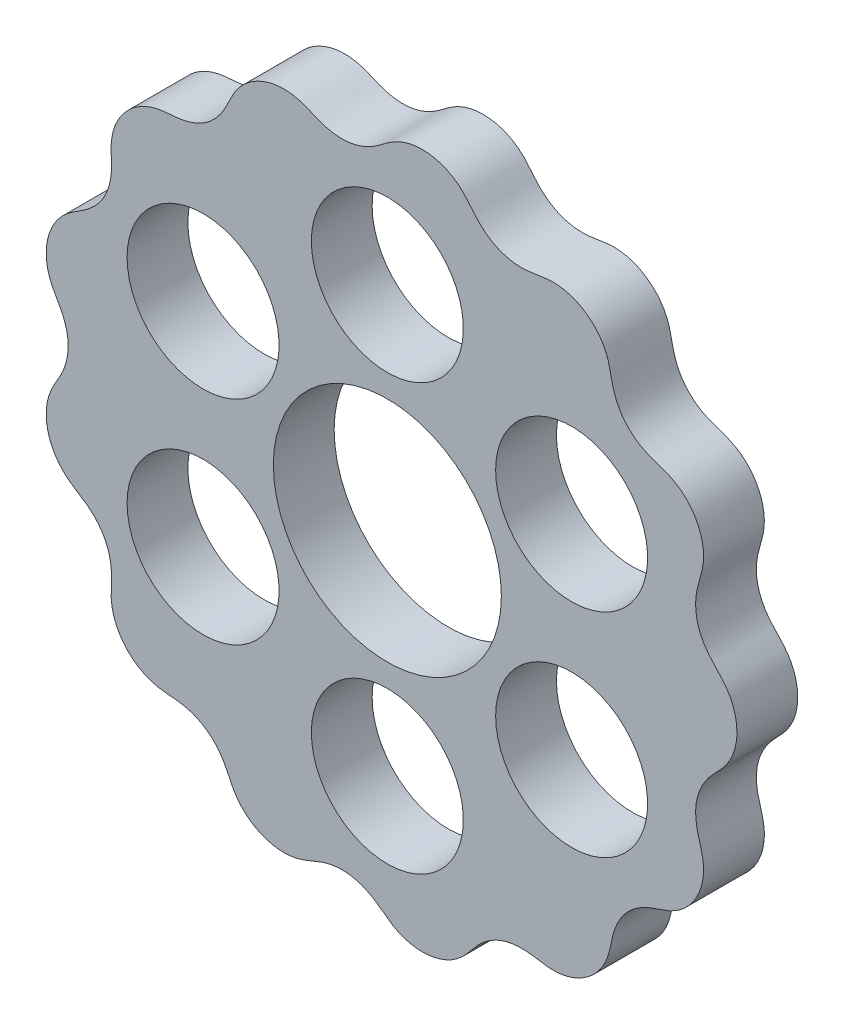
SolidWorks part; units mm, degrees
ref_plane "前视基准面" through (0, 0, 0) normal (0, 0, 1) x (1, 0, 0)
ref_plane "上视基准面" through (0, 0, 0) normal (0, 1, 0) x (1, 0, 0)
ref_plane "右视基准面" through (0, 0, 0) normal (1, 0, 0) x (0, 0, -1)
other "Configuration Table"
ref_axis "基准轴1" through (0, 0, 55) along (0, 0, -1)
sketch "LobeBaseSketch" plane through (0, 0, 0) normal (0, 0, 1) x (1, 0, 0)
  circle A0 centre (0, 0) radius 6.5
  spline S0 degree 3 number of poles 1043 (23, 0) -> (23, 0)
extrude "LobeBase" add sketch "LobeBaseSketch" along normal blind 4 and the other way blind 4
sketch "BoreRevolveSketch" plane through (0, 0, 0) normal (1, 0, 0) x (0, 0, -1)
  line L0 (0, 0) -> (1, 0) construction
  line L1 (-4, 0) -> (4, 0)
  line L2 (4, 0) -> (4, 6.5)
  line L3 (4, 6.5) -> (-4, 6.5)
  line L4 (-4, 6.5) -> (-4, 0)
  dimension "TaperSide1" = 6.5
  dimension "TaperSide2" = 6.5
sketch "AuxiliarySketchCycloidal01" plane through (0, 0, 0) normal (0, 0, 1) x (1, 0, 0)
  circle A0 centre (0, 0) radius 23.2143 construction
  circle A1 centre (25, 0) radius 1.7857 construction
  circle A2 centre (0, 0) radius 25 construction
  circle A3 centre (25, 0) radius 3 construction
  circle A4 centre (26, 0) radius 0.3 construction
  spline S0 degree 3 number of poles 81 (26, 0) -> (23.0219, 12.0828) construction
sketch "草图5" plane through (0, 0, 4) normal (0, 0, 1) x (1, 0, 0)
  circle A0 centre (0, 0) radius 14 construction
  circle A1 centre (0, 14) radius 5
  circle A2 centre (12.1244, 7) radius 5
  circle A3 centre (12.1244, -7) radius 5
  circle A4 centre (0, -14) radius 5
  circle A5 centre (-12.1244, -7) radius 5
  circle A6 centre (-12.1244, 7) radius 5
  point P17 (0, 0)
  dimension "D1" = 28
  dimension "D2" = 10
  dimension "D3" = 6
extrude "切除-拉伸1" cut sketch "草图5" against normal blind 10
sketch "草图6" plane through (0, 0, 4) normal (0, 0, 1) x (1, 0, 0)
  circle A0 centre (0, 0) radius 7.5
  dimension "D1" = 15
extrude "切除-拉伸2" cut sketch "草图6" against normal blind 10
sketch "草图7" plane through (0, 0, 4) normal (0, 0, 1) x (1, 0, 0)
  line L1 (-34.9139, -28.2491) -> (34.9139, -28.2491)
  line L2 (-34.9139, -28.2491) -> (-34.9139, 28.2491)
  line L3 (-34.9139, 28.2491) -> (34.9139, 28.2491)
  line L4 (34.9139, -28.2491) -> (34.9139, 28.2491)
  line L5 (-34.9139, -28.2491) -> (34.9139, 28.2491) construction
  line L6 (-34.9139, 28.2491) -> (34.9139, -28.2491) construction
  point P0 (0, 0)
extrude "切除-拉伸3" cut sketch "草图7" against normal blind 4
sketch "草图8" plane through (0, 0, 0) normal (0, 0, 1) x (1, 0, 0)
  line L0 (0, 0) -> (2.7723, 22.8323) construction
  line L1 (0, 0) -> (7.4467, 19.6353) construction
  spline S0 degree 3 number of poles 1043 (23, 0) -> (23, 0) construction
